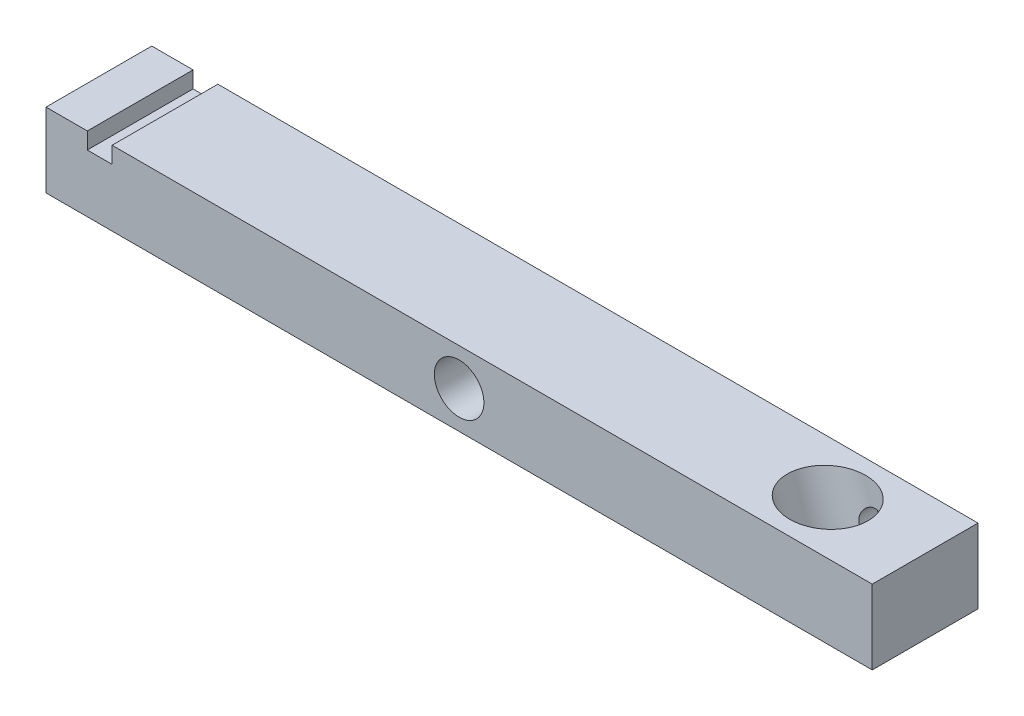
SolidWorks part; units mm, degrees
ref_plane "Front Plane" through (0, 0, 0) normal (0, 0, 1) x (1, 0, 0)
ref_plane "Top Plane" through (0, 0, 0) normal (0, 1, 0) x (1, 0, 0)
ref_plane "Right Plane" through (0, 0, 0) normal (1, 0, 0) x (0, 0, -1)
sketch "Sketch1" plane through (0, 0, 0) normal (0, 0, 1) x (1, 0, 0)
  line L1 (-63.5, -5.715) -> (63.5, -5.715)
  line L2 (-63.5, -5.715) -> (-63.5, 5.715)
  line L3 (-63.5, 5.715) -> (63.5, 5.715)
  line L4 (63.5, -5.715) -> (63.5, 5.715)
  line L5 (-63.5, -5.715) -> (63.5, 5.715) construction
  line L6 (-63.5, 5.715) -> (63.5, -5.715) construction
  point P0 (0, 0)
  dimension "D1" = 11.43
  dimension "D2" = 127
extrude "Boss-Extrude1" add sketch "Sketch1" along normal mid plane 16.256
sketch "Sketch6" plane through (0, 0, 8.128) normal (0, 0, 1) x (1, 0, 0)
  line L0 (-57.15, 5.715) -> (-57.15, 3.175)
  line L1 (43.18, -3.175) -> (43.18, -5.715)
  line L2 (-57.15, 3.175) -> (-53.34, 3.175)
  line L3 (-53.34, 3.175) -> (-53.34, 5.715)
  line L4 (-57.15, 5.715) -> (-53.34, 5.715)
  line L5 (63.5, 5.715) -> (-63.5, 5.715) construction
  line L6 (43.18, -5.715) -> (46.99, -5.715)
  line L7 (46.99, -5.715) -> (46.99, -3.175)
  line L8 (43.18, -3.175) -> (46.99, -3.175)
  line L9 (-63.5, -5.715) -> (63.5, -5.715) construction
  dimension "D4" = 2.54
  dimension "D1" = 53.34
  dimension "D2" = 2.54
  dimension "D3" = 57.15
  dimension "D5" = 43.18
  dimension "D6" = 3.81
extrude "Cut-Extrude1" cut sketch "Sketch6" against normal up to surface (16.256 mm away) contours L4 L3 L2 L0 up to face at (0, 0, -8.128)
sketch "Sketch12" plane through (0, 0, 8.128) normal (0, 0, 1) x (1, 0, 0)
  circle A0 centre (0, 0) radius 3.81
  dimension "D1" = 7.62
extrude "Cut-Extrude2" cut sketch "Sketch12" against normal up to surface (16.256 mm away) up to face at (-27.6225, 2.2225, -8.128)
ref_plane "Plane1" through (9.2649, -25.455, 0) normal (0.342, -0.9397, 0) x (0, 0, -1)
sketch "Sketch14" plane through (9.2649, -25.455, 0) normal (0.342, -0.9397, 0) x (0, 0, -1)
  line L0 (-8.128, 57.7158) -> (8.128, 57.7158) construction
  line L1 (0, -11.2201) -> (0, 68.737) construction
  circle A0 centre (0, 47.5558) radius 5.842
  point P2 (0, 50.1283)
  dimension "D1" = 11.684
  dimension "D2" = 10.16
extrude "Cut-Extrude3" cut sketch "Sketch14" against normal blind 25.4
sketch "Sketch17" plane through (0, 0, -8.128) normal (0, 0, -1) x (-1, 0, 0)
  circle A0 centre (-50.0486, 0) radius 2.032
  dimension "D1" = 4.064
extrude "Cut-Extrude4" cut sketch "Sketch17" against normal up to surface (2.8176 mm away) up to face at (58.9049, -5.715, 0)
